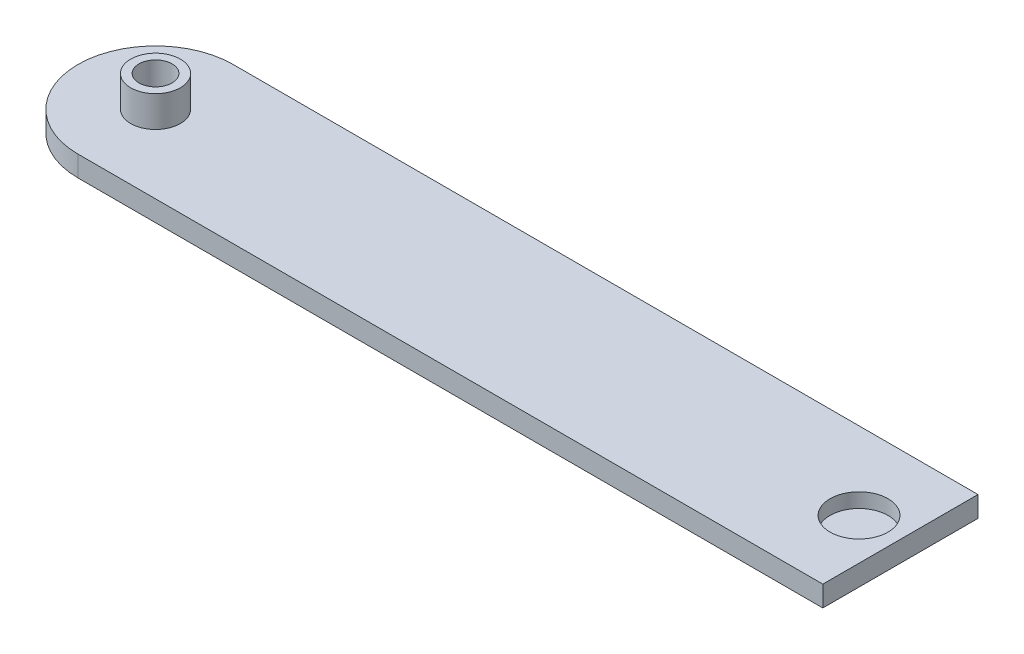
SolidWorks part; units mm, degrees
ref_plane "Front Plane" through (0, 0, 0) normal (0, 0, 1) x (1, 0, 0)
ref_plane "Top Plane" through (0, 0, 0) normal (0, 1, 0) x (1, 0, 0)
ref_plane "Right Plane" through (0, 0, 0) normal (1, 0, 0) x (0, 0, -1)
sketch "Sketch1" plane through (0, 0, 0) normal (0, 1, 0) x (1, 0, 0)
  line L1 (0, -7.5) -> (72, -7.5)
  line L2 (0, -7.5) -> (0, 7.5)
  line L3 (0, 7.5) -> (72, 7.5)
  line L4 (72, -7.5) -> (72, 7.5)
  circle A0 centre (0, 0) radius 7.5
  dimension "D1" = 15
  dimension "D2" = 72
  dimension "D3" = 15
extrude "Boss-Extrude1" add sketch "Sketch1" along normal blind 2 contours A0 L1 L4 L3 | L2 A0 | L2 A0 region at (38.924, 0, 0) region at (-3.1831, 0, 0) region at (3.1831, 0, 0)
sketch "Sketch2" plane through (0, 2, 0) normal (0, 1, 0) x (1, 0, 0)
  circle A0 centre (0, 0) radius 1.6
extrude "Cut-Extrude1" cut sketch "Sketch2" against normal blind 1.8
sketch "Sketch3" plane through (0, 0.2, 0) normal (0, 1, 0) x (1, 0, 0)
  circle A0 centre (0, 0) radius 0.8
extrude "Cut-Extrude2" cut sketch "Sketch3" against normal blind 3
sketch "Sketch4" plane through (0, 2, 0) normal (0, 1, 0) x (1, 0, 0)
  line L0 (72, -7.5) -> (72, 7.5) construction
  circle A0 centre (68, 0) radius 2.8
  point P5 (72, 0)
  dimension "D1" = 4
extrude "Cut-Extrude3" cut sketch "Sketch4" against normal blind 1.4
sketch "Sketch5" plane through (0, 2, 0) normal (0, 1, 0) x (1, 0, 0)
  circle A0 centre (0, 0) radius 2.4
  circle A1 centre (0, 0) radius 1.6
extrude "Boss-Extrude2" add sketch "Sketch5" along normal blind 3
